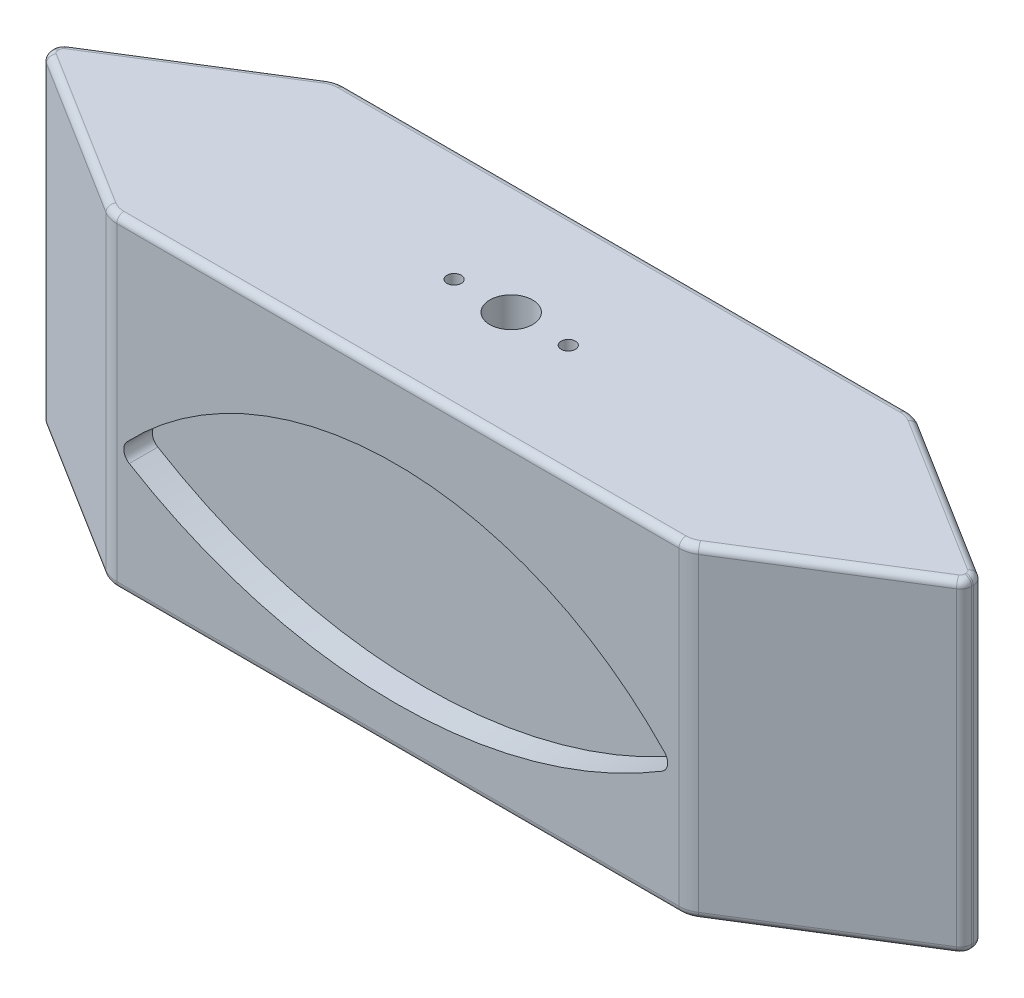
SolidWorks part; units mm, degrees
ref_plane "Front Plane" through (0, 0, 0) normal (0, 0, 1) x (1, 0, 0)
ref_plane "Top Plane" through (0, 0, 0) normal (0, 1, 0) x (1, 0, 0)
ref_plane "Right Plane" through (0, 0, 0) normal (1, 0, 0) x (0, 0, -1)
sketch "Sketch1" plane through (0, 0, 0) normal (0, 0, 1) x (1, 0, 0)
  line L1 (0, 402.8482) -> (204.95, 402.8482)
  line L2 (0, 402.8482) -> (0, 330.6895)
  line L3 (0, 330.6895) -> (204.95, 330.6895)
  line L4 (204.95, 402.8482) -> (204.95, 330.6895)
extrude "Boss-Extrude1" add sketch "Sketch1" along normal blind 25.4 and the other way blind 25.4
sketch "Sketch2" plane through (0, 402.8482, 0) normal (0, 1, 0) x (1, 0, 0)
  line L0 (1.1938, -2.3336) -> (36.5557, -24.4348)
  line L1 (0, 25.4) -> (0, -25.4) construction
  line L2 (204.95, -25.4) -> (0, -25.4) construction
  line L3 (39.9212, -25.4) -> (165.0289, -25.4)
  line L4 (168.3944, -24.4348) -> (203.7562, -2.3336)
  line L5 (204.95, 25.4) -> (204.95, -25.4) construction
  line L6 (204.95, -0.1797) -> (204.95, 0.1797)
  line L7 (203.7562, 2.3336) -> (168.3944, 24.4348)
  line L8 (204.95, 25.4) -> (0, 25.4) construction
  line L9 (165.0289, 25.4) -> (39.9212, 25.4)
  line L10 (36.5557, 24.4348) -> (1.1938, 2.3336)
  line L11 (0, 0.1797) -> (0, -0.1797)
  line L13 (-8.7001, 38.6118) -> (211.905, 38.6118)
  line L14 (-8.7001, 38.6118) -> (-8.7001, -37.946)
  line L15 (-8.7001, -37.946) -> (211.905, -37.946)
  line L16 (211.905, 38.6118) -> (211.905, -37.946)
  arc A0 (168.3944, 24.4348) -> (165.0289, 25.4) centre (165.0289, 19.05) ccw
  arc A1 (165.0289, -25.4) -> (168.3944, -24.4348) centre (165.0289, -19.05) ccw
  arc A2 (36.5557, -24.4348) -> (39.9212, -25.4) centre (39.9212, -19.05) ccw
  arc A3 (39.9212, 25.4) -> (36.5557, 24.4348) centre (39.9212, 19.05) ccw
  arc A4 (204.95, 0.1797) -> (203.7562, 2.3336) centre (202.41, 0.1797) ccw
  arc A5 (203.7562, -2.3336) -> (204.95, -0.1797) centre (202.41, -0.1797) ccw
  arc A6 (1.1938, -2.3336) -> (0, -0.1797) centre (2.54, -0.1797) cw
  arc A7 (1.1938, 2.3336) -> (0, 0.1797) centre (2.54, 0.1797) ccw
  circle A8 centre (102.475, -0.1797) radius 4.7625
  point P23 (166.85, 25.4)
  point P26 (166.85, -25.4)
  point P29 (38.1, -25.4)
  point P32 (38.1, 25.4)
  point P35 (204.95, 1.5875)
  point P38 (204.95, -1.5875)
  point P41 (0, -1.5875)
  point P44 (0, 1.5875)
  point P47 (102.475, -25.4)
  line M1 (0, 25.4) -> (0, -25.4)
  line M2 (0, -25.4) -> (204.95, -25.4)
  line M3 (204.95, -25.4) -> (204.95, 25.4)
  line M4 (204.95, 25.4) -> (0, 25.4)
  dimension "D4" = 6.35
  dimension "D5" = 2.54
  dimension "D6" = 9.525
  dimension "D1" = 1.5875
  dimension "D2" = 3.175
  dimension "D3" = 38.1
extrude "Cut-Extrude1" cut sketch "Sketch2" against normal through all contours A7 L10 A3 M4 M1 | L16 L13 L14 L15 M1 M4 M3 M2 | L0 A6 A2 M1 M2 | A5 L4 A1 M2 M3 | A4 A0 L7 M3 M4 | A8 region at (12.7084, 402.8482, 17.4567) region at (12.7084, 402.8482, -17.4567) region at (192.2416, 402.8482, 17.4567) region at (192.2416, 402.8482, -17.4567) region at (101.6024, 402.8482, -36.2767) region at (102.475, 402.8482, 0.1797)
fillet "Fillet1" radius 1.5875 32 edges at (38.1706, 330.6895, 25.1539) (18.8747, 330.6895, 13.3842) (0.3184, 330.6895, 1.411) (0, 330.6895, 0) (0.3184, 330.6895, -1.411) (18.8747, 330.6895, -13.3842) (38.1706, 330.6895, -25.1539) (102.475, 330.6895, -25.4) (166.7795, 330.6895, -25.1539) (186.0753, 330.6895, -13.3842) (204.6316, 330.6895, -1.411) (204.95, 330.6895, 0) (204.6316, 330.6895, 1.411) (186.0753, 330.6895, 13.3842) (166.7795, 330.6895, 25.1539) (0.3184, 402.8482, 1.411) (0, 402.8482, 0) (0.3184, 402.8482, -1.411) (18.8747, 402.8482, -13.3842) (38.1706, 402.8482, -25.1539) (102.475, 402.8482, -25.4) (166.7795, 402.8482, -25.1539) (186.0753, 402.8482, -13.3842) (204.6316, 402.8482, -1.411) (204.95, 402.8482, 0) (204.6316, 402.8482, 1.411) (186.0753, 402.8482, 13.3842) (166.7795, 402.8482, 25.1539) (102.475, 402.8482, 25.4) (38.1706, 402.8482, 25.1539) (102.475, 330.6895, 25.4) (18.8747, 402.8482, 13.3842)
sketch "Sketch3" plane through (0, 0, 25.4) normal (0, 0, 1) x (1, 0, 0)
  arc A0 (42.1794, 360.3412) -> (161.8178, 360.3412) centre (101.9986, 303.4539) cw
  arc A1 (42.7023, 356.4194) -> (161.295, 356.4194) centre (101.9986, 454.1355) ccw
  arc A2 (161.8178, 360.3412) -> (161.295, 356.4194) centre (159.9773, 358.5908) cw
  arc A3 (42.1794, 360.3412) -> (42.7023, 356.4194) centre (44.02, 358.5908) ccw
  point P8 (163.9111, 358.0556)
  point P11 (40.0861, 358.0556)
  dimension "D2" = 82.55
  dimension "D3" = 114.3
  dimension "D4" = 2.54
  dimension "D1" = 123.825
extrude "Cut-Extrude2" cut sketch "Sketch3" against normal blind 6.35 contours A1 A2 A0 A3
mirror "Mirror1" about plane through (0, 0, 0) normal (0, 0, 1) of "Cut-Extrude2"
sketch "Sketch4" plane through (0, 330.6895, 0) normal (0, -1, 0) x (1, 0, 0)
  circle A0 centre (92.95, 0.1797) radius 1.5875
  circle A1 centre (112, 0.1797) radius 1.5875
  circle A2 centre (102.475, 0.1797) radius 4.7625 construction
  dimension "D1" = 9.525
  dimension "D2" = 9.525
  dimension "D3" = 3.175
  dimension "D4" = 3.175
extrude "Cut-Extrude3" cut sketch "Sketch4" against normal blind 12.7
sketch "Sketch5" plane through (0, 402.8482, 0) normal (0, 1, 0) x (1, 0, 0)
  circle A0 centre (89.775, -0.1797) radius 1.5875
  circle A1 centre (115.175, -0.1797) radius 1.5875
  circle A2 centre (102.475, -0.1797) radius 4.7625 construction
  dimension "D1" = 12.7
  dimension "D2" = 12.7
  dimension "D3" = 3.175
extrude "Cut-Extrude4" cut sketch "Sketch5" against normal blind 12.7
